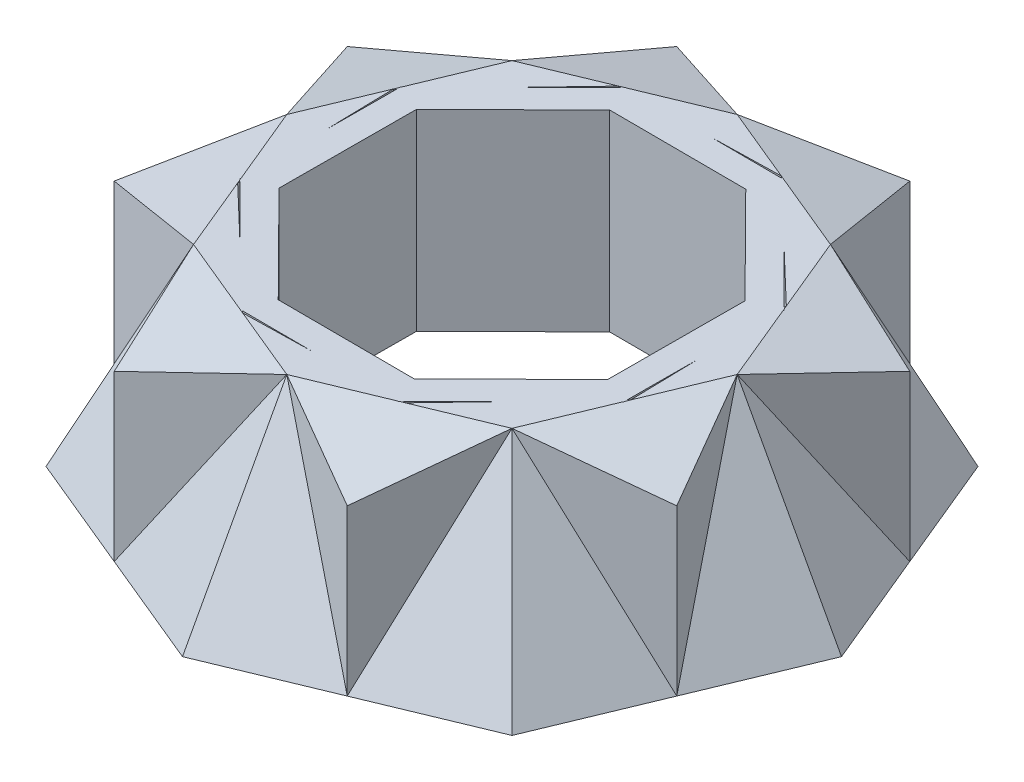
SolidWorks part; units mm, degrees
ref_plane "前视基准面" through (0, 0, 0) normal (0, 0, 1) x (1, 0, 0)
ref_plane "上视基准面" through (0, 0, 0) normal (0, 1, 0) x (1, 0, 0)
ref_plane "右视基准面" through (0, 0, 0) normal (1, 0, 0) x (0, 0, -1)
other "Configuration Table"
sketch "草图1" plane through (0, 0, 0) normal (0, 1, 0) x (1, 0, 0)
  line L0 (0, 60) -> (-42.4264, 42.4264)
  line L13 (-60, 0) -> (-42.4264, -42.4264)
  line L14 (-42.4264, -42.4264) -> (0, -60)
  line L15 (0, -60) -> (42.4264, -42.4264)
  line L16 (42.4264, -42.4264) -> (60, 0)
  line L17 (60, 0) -> (42.4264, 42.4264)
  line L18 (42.4264, 42.4264) -> (0, 60)
  line L19 (-42.4264, 42.4264) -> (-60, 0)
  line L20 (-15.2788, 34.6749) -> (-35.3226, 13.7152)
  line L21 (-13.0966, 29.7224) -> (-30.2776, 11.7563)
  line L22 (-30.2776, 11.7563) -> (-29.7224, -13.0966)
  line L23 (-29.7224, -13.0966) -> (-11.7563, -30.2776)
  line L24 (-11.7563, -30.2776) -> (13.0966, -29.7224)
  line L25 (13.0966, -29.7224) -> (30.2776, -11.7563)
  line L26 (30.2776, -11.7563) -> (29.7224, 13.0966)
  line L27 (29.7224, 13.0966) -> (11.7563, 30.2776)
  line L28 (11.7563, 30.2776) -> (-13.0966, 29.7224)
  line L29 (-35.3226, 13.7152) -> (-34.6749, -15.2788)
  line L30 (-34.6749, -15.2788) -> (-13.7152, -35.3226)
  line L31 (-13.7152, -35.3226) -> (15.2788, -34.6749)
  line L32 (15.2788, -34.6749) -> (35.3226, -13.7152)
  line L33 (35.3226, -13.7152) -> (34.6749, 15.2788)
  line L34 (34.6749, 15.2788) -> (13.7152, 35.3226)
  line L35 (13.7152, 35.3226) -> (-15.2788, 34.6749)
  circle A0 centre (0, 0) radius 55.4328 construction
  circle A1 centre (0, 0) radius 30.0075 construction
  point P28 (0, 0)
  dimension "D1" = 120
  dimension "D2" = 60
  dimension "D3" = 5
extrude "凸台-拉伸1" add sketch "草图1" along normal blind 35 contours L0 L19 L13 L14 L15 L16 L17 L18 L35 L34 L33 L32 L31 L30 L29 L20 region at (20.5638, 0, -49.6453)
ref_axis "基准轴1" through (0, -1.75, 0) along (0, 1, 0)
ref_plane "基准面1" through (16.951, 22.2113, 40.9234) normal (-0.3421, -0.4482, -0.8259) x (-0.9397, 0.1632, 0.3007)
sketch "草图2" plane through (16.951, 22.2113, 40.9234) normal (-0.3421, -0.4482, -0.8259) x (-0.9397, 0.1632, 0.3007)
  line L1 (-84.6151, -37.2276) -> (84.6151, -37.2276)
  line L2 (-84.6151, -37.2276) -> (-84.6151, 37.2276)
  line L3 (-84.6151, 37.2276) -> (84.6151, 37.2276)
  line L4 (84.6151, -37.2276) -> (84.6151, 37.2276)
  line L5 (-84.6151, -37.2276) -> (84.6151, 37.2276) construction
  line L6 (-84.6151, 37.2276) -> (84.6151, -37.2276) construction
  point P0 (0, 0)
extrude "切除-拉伸1" cut sketch "草图2" against normal blind 35
pattern_circular "阵列(圆周)1" count 8 over 360 about axis through (0, -1.75, 0) along (0, 1, 0) of "切除-拉伸1"
sketch "草图4" plane through (0, 35, 0) normal (0, 1, 0) x (1, 0, 0)
  line L0 (-28.9939, 28.9939) -> (-41.0036, 0)
  line L1 (-41.0036, 0) -> (-51.2132, 21.2132)
  line L2 (-42.4264, 42.4264) -> (-60, 0) construction
  line L3 (-51.2132, 21.2132) -> (-28.9939, 28.9939)
extrude "凸台-拉伸3" add sketch "草图4" against normal up to surface (35 mm away) separate body up to face at (-41.5493, 21, -17.0271)
ref_plane "基准面3" through (0, 30, 0) normal (0, 1, 0) x (1, 0, 0)
sketch "草图7" plane through (0, 30, 0) normal (0, 1, 0) x (1, 0, 0)
  line L0 (-42.4264, 42.4264) -> (-60, 0) construction
  point P0 (-51.2132, 21.2132)
ref_plane "基准面4" through (-11.1481, 42.3548, -4.6177) normal (-0.2531, 0.9617, -0.1049) x (0.9674, 0.2516, -0.0274)
sketch "草图8" plane through (-11.1481, 42.3548, -4.6177) normal (-0.2531, 0.9617, -0.1049) x (0.9674, 0.2516, -0.0274)
  line L1 (6.7364, -8.8387) -> (-66.2076, -8.8387)
  line L2 (6.7364, -8.8387) -> (6.7364, 34.6483)
  line L3 (6.7364, 34.6483) -> (-66.2076, 34.6483)
  line L4 (-66.2076, -8.8387) -> (-66.2076, 34.6483)
  line L5 (6.7364, -8.8387) -> (-66.2076, 34.6483) construction
  line L6 (6.7364, 34.6483) -> (-66.2076, -8.8387) construction
  point P0 (-29.7356, 12.9048)
extrude "切除-拉伸2" cut sketch "草图8" along normal blind 41
pattern_circular "阵列(圆周)2" count 8 over 360 about axis through (0, -1.75, 0) along (0, 1, 0) of bodies 129
sketch "草图9" plane through (0, 0, 0) normal (0, 1, 0) x (1, 0, 0)
  line L0 (12.327, -30.0994) -> (30, -12.567)
  line L1 (30.0994, 12.327) -> (12.567, 30)
  line L2 (12.567, 30) -> (-12.327, 30.0994)
  line L3 (-12.327, 30.0994) -> (-30, 12.567)
  line L4 (-30, 12.567) -> (-30.0994, -12.327)
  line L5 (-30.0994, -12.327) -> (-12.567, -30)
  line L6 (-12.567, -30) -> (12.327, -30.0994)
  line L7 (30, -12.567) -> (30.0994, 12.327)
  line L8 (-34.9917, 14.658) -> (-35.1076, -14.3781)
  line L9 (-35.1076, -14.3781) -> (-14.658, -34.9917)
  line L10 (-14.658, -34.9917) -> (14.3781, -35.1076)
  line L11 (14.3781, -35.1076) -> (34.9917, -14.658)
  line L12 (34.9917, -14.658) -> (35.1076, 14.3781)
  line L13 (35.1076, 14.3781) -> (14.658, 34.9917)
  line L14 (14.658, 34.9917) -> (-14.3781, 35.1076)
  line L15 (-14.3781, 35.1076) -> (-34.9917, 14.658)
  circle A0 centre (0, 0) radius 30.0499 construction
  point P1 (42.4264, 0)
  point P12 (12.6588, 40.4939)
  point P13 (30, 12.361)
  point P14 (0, 0)
  point P23 (30, 12.567)
  dimension "D1" = 60
  dimension "D2" = 5
extrude "凸台-拉伸5" add sketch "草图9" along normal blind 35
